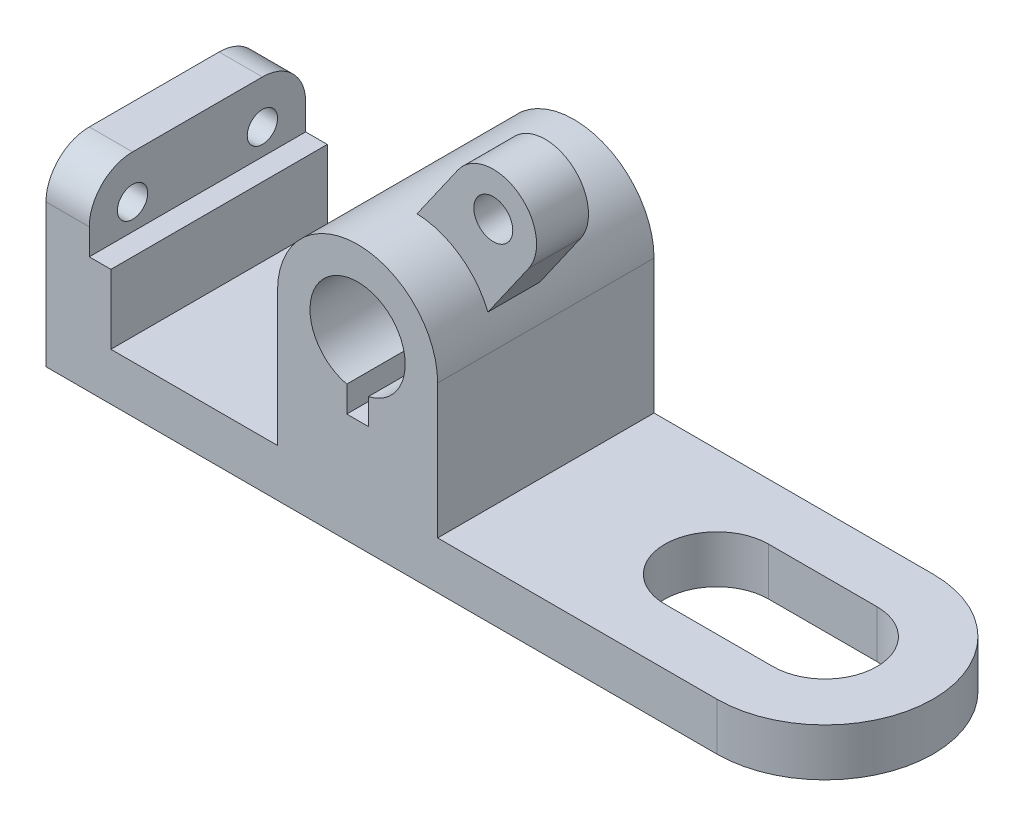
SolidWorks part; units mm, degrees
ref_plane "Front Plane" through (0, 0, 0) normal (0, 0, 1) x (1, 0, 0)
ref_plane "Top Plane" through (0, 0, 0) normal (0, 1, 0) x (1, 0, 0)
ref_plane "Right Plane" through (0, 0, 0) normal (1, 0, 0) x (0, 0, -1)
sketch "Sketch1" plane through (0, 0, 0) normal (0, 0, 1) x (1, 0, 0)
  line L0 (0, 0) -> (25, 0)
  line L1 (0, 0) -> (-155, 0)
  line L2 (-155, 0) -> (-155, 43)
  line L3 (-155, 43) -> (-145, 43)
  line L4 (-145, 43) -> (-145, 27)
  line L5 (-145, 27) -> (-140, 27)
  line L6 (-140, 27) -> (-140, 11)
  line L7 (-140, 11) -> (-101.5, 11)
  line L8 (-101.5, 11) -> (-101.5, 42)
  line L9 (-64.5, 42) -> (-64.5, 11)
  line L10 (-64.5, 11) -> (25, 11)
  line L11 (25, 11) -> (25, 0)
  line L12 (-83, 42) -> (-46.0884, 42) construction
  line L13 (-83, 42) -> (-64.6456, 68.2129) construction
  line L14 (-72.8371, 73.9486) -> (-82.2642, 60.4854)
  line L15 (-56.454, 62.4771) -> (-65.8811, 49.0138)
  line L16 (-83, 42) -> (-83, 25.2879) construction
  line L17 (-85.5, 25.2879) -> (-80.5, 25.2879)
  line L18 (-85.5, 25.2879) -> (-85.5, 31.2879)
  line L19 (-80.5, 25.2879) -> (-80.5, 31.2879)
  line L20 (-85.5, 31.2879) -> (-80.5, 31.2879)
  arc A0 (-101.5, 42) -> (-64.5, 42) centre (-83, 42) cw
  circle A1 centre (-64.6456, 68.2129) radius 4.5
  arc A2 (-56.454, 62.4771) -> (-72.8371, 73.9486) centre (-64.6456, 68.2129) ccw
  arc A3 (-80.5, 31.2879) -> (-85.5, 31.2879) centre (-83, 42) ccw
  point P23 (-83, 31)
  point P28 (-83, 25.2879)
  dimension "D1" = 55
  dimension "D2" = 32
  dimension "D3" = 11
  dimension "D11" = 5
  dimension "D12" = 22
  dimension "D13" = 18.5
  dimension "D14" = 10
  dimension "D15" = 9
  dimension "D4" = 43
  dimension "D5" = 16
  dimension "D6" = 15
  dimension "D7" = 5
  dimension "D8" = 72
  dimension "D9" = 155
  dimension "D10" = 25
  dimension "D16" = 6
  dimension "D17" = 42
extrude "Boss-Extrude1" add sketch "Sketch1" along normal mid plane 50 contours A0 L8 L7 L6 L5 L4 L3 L2 L1 L0 L11 L10 L9 A3 L19 L17 L18 region at (-80.4175, 16.8138, 0)
sketch "Sketch2" plane through (0, 11, 0) normal (0, 1, 0) x (1, 0, 0)
  line L0 (-64.5, 25) -> (25, 25) construction
  line L1 (0, 0) -> (-25, 0) construction
  line L2 (-25, 12) -> (0, 12)
  line L3 (-25, -12) -> (0, -12)
  line L4 (0, 25) -> (-64.5, 25)
  line L5 (-64.5, 25) -> (-64.5, -25)
  line L6 (-64.5, -25) -> (0, -25)
  line L7 (25, -25) -> (25, 25)
  line L8 (25, 25) -> (0, 25)
  arc A0 (0, 12) -> (0, -12) centre (0, 0) cw
  arc A1 (-25, 12) -> (-25, -12) centre (-25, 0) ccw
  arc A2 (0, 25) -> (0, -25) centre (0, 0) cw
  line M1 (25, 25) -> (-64.5, 25)
  line M3 (-64.5, -25) -> (25, -25)
  line M4 (25, -25) -> (25, 25)
  dimension "D1" = 13
  dimension "D2" = 25
extrude "Cut-Extrude1" cut sketch "Sketch2" against normal up to surface (11 mm away) contours A2 L7 M1 | A2 M4 M3 | L2 A1 L3 A0 region at (-12.5, 11, 0) region at (19.4158, 11, -19.4158) region at (19.4158, 11, 19.4158) up to face at (-65, 0, 0)
extrude "Boss-Extrude2" add sketch "Sketch1<3>" along normal blind 12 contours L15 A2 L14 A0 A1 region at (-72.1583, 57.4835, 0)
sketch "Sketch1<3>" plane through (0, 0, 0) normal (0, 0, 1) x (1, 0, 0) same geometry as "Sketch1"
sketch "Sketch3" plane through (-155, 0, 0) normal (-1, 0, 0) x (0, 0, 1)
  line L0 (-25, 0) -> (-25, 33)
  line L1 (-15, 43) -> (15, 43)
  line L2 (25, 33) -> (25, 0)
  line L3 (25, 0) -> (-25, 0)
  line L4 (-25, 33) -> (-25, 43)
  line L5 (-25, 43) -> (25, 43)
  line L6 (25, 43) -> (25, 33)
  arc A0 (25, 33) -> (15, 43) centre (15, 33) ccw
  arc A1 (-25, 33) -> (-15, 43) centre (-15, 33) cw
  circle A2 centre (-15, 33) radius 3.5
  circle A3 centre (15, 33) radius 3.5
  point P10 (25, 43)
  point P13 (-25, 43)
  line M7 (-25, 43) -> (-25, 0)
  line M9 (25, 0) -> (25, 43)
  line M10 (25, 43) -> (-25, 43)
  dimension "D1" = 10
  dimension "D2" = 7
  dimension "D3" = 7
extrude "Cut-Extrude2" cut sketch "Sketch3" against normal up to surface (10 mm away) contours A1 M7 M10 | A0 M9 M10 | A2 | A3 region at (-155, 40.7663, -22.7663) region at (-155, 40.7663, 22.7663) up to face at (-145, 35, 0)
